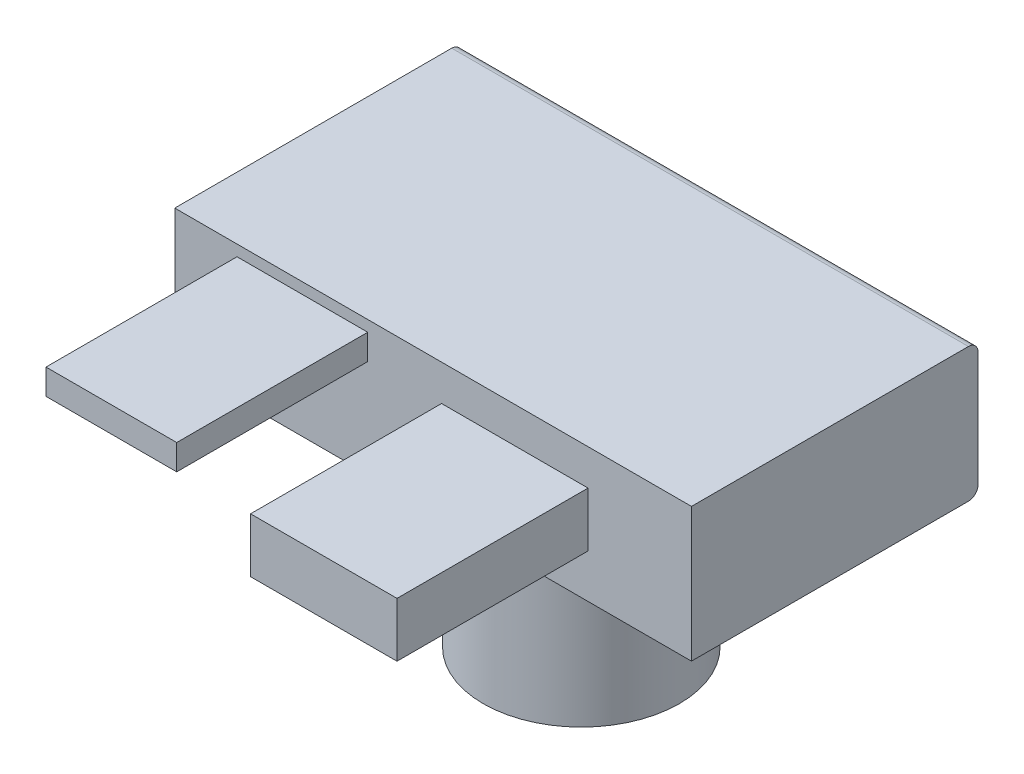
SolidWorks part; units mm, degrees
ref_plane "Front Plane" through (0, 0, 0) normal (0, 0, 1) x (1, 0, 0)
ref_plane "Top Plane" through (0, 0, 0) normal (0, 1, 0) x (1, 0, 0)
ref_plane "Right Plane" through (0, 0, 0) normal (1, 0, 0) x (0, 0, -1)
sketch "Sketch1" plane through (0, 0, 0) normal (0, 0, 1) x (1, 0, 0)
  line L1 (-68.7035, -17.821) -> (68.7035, -17.821)
  line L2 (-68.7035, -17.821) -> (-68.7035, 17.821)
  line L3 (-68.7035, 17.821) -> (68.7035, 17.821)
  line L4 (68.7035, -17.821) -> (68.7035, 17.821)
  line L5 (-68.7035, -17.821) -> (68.7035, 17.821) construction
  line L6 (-68.7035, 17.821) -> (68.7035, -17.821) construction
  point P0 (0, 0)
extrude "Boss-Extrude1" add sketch "Sketch1" along normal blind 76.2 contours L1 L4 L3 L2
sketch "Sketch2" plane through (0, 17.821, 0) normal (0, 1, 0) x (1, 0, 0)
  line L1 (23.159, -37.2907) -> (11.1437, -16.4796)
  line L2 (11.1437, -16.4796) -> (-12.8869, -16.4796)
  line L3 (-12.8869, -16.4796) -> (-24.9022, -37.2907)
  line L4 (-24.9022, -37.2907) -> (-12.8869, -58.1018)
  line L5 (-12.8869, -58.1018) -> (11.1437, -58.1018)
  line L6 (11.1437, -58.1018) -> (23.159, -37.2907)
  circle A0 centre (-0.8716, -37.2907) radius 20.8111 construction
sketch "Sketch3" plane through (0, -17.821, 0) normal (0, -1, 0) x (1, 0, 0)
  circle A0 centre (0, 36.7926) radius 26.0998
extrude "Boss-Extrude3" add sketch "Sketch3" along normal blind 50.8
sketch "Sketch4" plane through (0, 0, 76.2) normal (0, 0, 1) x (1, 0, 0)
  line L1 (-52.1439, 14.8868) -> (-17.3813, 14.8868)
  line L2 (-52.1439, 14.8868) -> (-52.1439, 8.1274)
  line L3 (-52.1439, 8.1274) -> (-17.3813, 8.1274)
  line L4 (-17.3813, 14.8868) -> (-17.3813, 8.1274)
  line L5 (-52.1439, 14.8868) -> (-17.3813, 8.1274) construction
  line L6 (-52.1439, 8.1274) -> (-17.3813, 14.8868) construction
  line L7 (2.2531, 8.2883) -> (41.2001, 8.2883)
  line L8 (2.2531, 8.2883) -> (2.2531, -6.1961)
  line L9 (2.2531, -6.1961) -> (41.2001, -6.1961)
  line L10 (41.2001, 8.2883) -> (41.2001, -6.1961)
  line L11 (2.2531, 8.2883) -> (41.2001, -6.1961) construction
  line L12 (2.2531, -6.1961) -> (41.2001, 8.2883) construction
  point P0 (-34.7626, 11.5071)
  point P5 (21.7266, 1.0461)
extrude "Boss-Extrude4" add sketch "Sketch4" along normal blind 50.8
fillet "Fillet1" radius 2.54 1 edges at (0, -17.821, 10.6929)
fillet "Fillet2" radius 2.54 2 edges at (0, -17.821, 0) (0, 17.821, 0)
